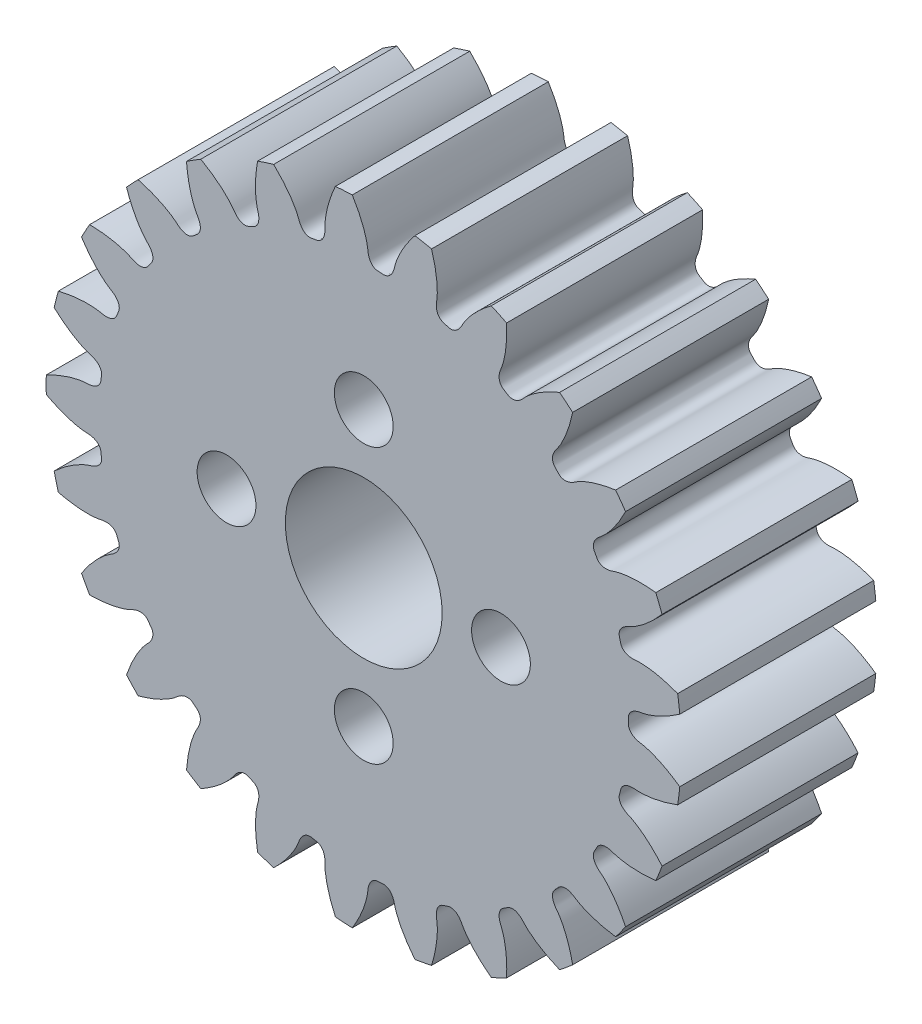
SolidWorks part; units mm, degrees
material "Д16 ГОСТ 4784-97"
ref_plane "FRONT" through (0, 0, 0) normal (0, 0, 1) x (1, 0, 0)
ref_plane "TOP" through (0, 0, 0) normal (0, 1, 0) x (1, 0, 0)
ref_plane "RIGHT" through (0, 0, 0) normal (1, 0, 0) x (0, 0, -1)
ref_axis "Ось1" through (0, 0, 50) along (0, 0, -1)
sketch "SketchRevolveSpurPinion" plane through (0, 0, 0) normal (1, 0, 0) x (0, 0, -1)
  line L0 (0, 0) -> (1, 0) construction
  line L1 (-5, 0) -> (-5, 16.2)
  line L2 (-5, 16.2) -> (5, 16.2)
  line L3 (5, 16.2) -> (5, 0)
  line L4 (5, 0) -> (-5, 0)
revolve "SpurPinion" add sketch "SketchRevolveSpurPinion" angle 360 about L0
sketch "SketchToothSpurPinion" plane through (0, 0, 0) normal (0, 0, 1) x (1, 0, 0)
  arc A0 (16.1769, 1.6413) -> (16.1769, -1.6413) centre (0, 0) cw
  spline S0 degree 3 poles (16.1769, -1.6413) (16.0571, -1.5552) (15.8785, -1.4341) (15.6403, -1.2876) (15.4737, -1.1915) (15.3146, -1.1059) (15.1636, -1.03) (15.021, -0.9635) (14.8873, -0.9057) (14.7627, -0.8561) (14.6478, -0.814) (14.5428, -0.779) (14.4479, -0.7504) (14.3636, -0.7275) (14.2899, -0.7099) (14.1891, -0.6884) (14.1006, -0.6766) (14.0235, -0.6588) (13.9906, -0.6504) (13.9585, -0.6412) (13.9271, -0.6311) (13.8962, -0.6202) (13.8659, -0.6084) (13.8361, -0.5955) (13.8068, -0.5814) (13.7778, -0.5661) (13.7492, -0.5492) (13.7209, -0.5305) (13.6928, -0.5098) (13.6651, -0.4868) (13.6378, -0.4609) (13.6112, -0.4318) (13.5856, -0.3991) (13.5616, -0.3622) (13.5401, -0.321) (13.522, -0.2755) (13.5085, -0.2261) (13.5011, -0.1771) (13.4979, -0.1014) (13.5016, 0) (13.4979, 0.1014) (13.5011, 0.1771) (13.5085, 0.2261) (13.522, 0.2755) (13.5401, 0.321) (13.5616, 0.3622) (13.5856, 0.3991) (13.6112, 0.4318) (13.6378, 0.4609) (13.6651, 0.4868) (13.6928, 0.5098) (13.7209, 0.5305) (13.7492, 0.5492) (13.7778, 0.5661) (13.8068, 0.5814) (13.8361, 0.5955) (13.8659, 0.6084) (13.8962, 0.6202) (13.9271, 0.6311) (13.9585, 0.6412) (13.9906, 0.6504) (14.0235, 0.6588) (14.1006, 0.6766) (14.1891, 0.6884) (14.2899, 0.7099) (14.3636, 0.7275) (14.4479, 0.7504) (14.5428, 0.779) (14.6478, 0.814) (14.7627, 0.8561) (14.8873, 0.9057) (15.021, 0.9635) (15.1636, 1.03) (15.3146, 1.1059) (15.4737, 1.1915) (15.6403, 1.2876) (15.8785, 1.4341) (16.0571, 1.5552) (16.1769, 1.6413) knots 0 0 0 0 0.066592 0.09726 0.126175 0.153338 0.178748 0.202406 0.224312 0.244465 0.262865 0.279513 0.294409 0.307552 0.318943 0.328581 0.35401 0.359185 0.364277 0.369297 0.374256 0.379169 0.384052 0.388923 0.393806 0.398725 0.40371 0.408794 0.414018 0.419423 0.425056 0.430965 0.437198 0.443793 0.450773 0.458134 0.46584 0.473813 0.480451 0.5 0.519549 0.526187 0.53416 0.541866 0.549227 0.556207 0.562802 0.569035 0.574944 0.580577 0.585982 0.591206 0.59629 0.601275 0.606194 0.611077 0.615948 0.620831 0.625744 0.630703 0.635723 0.640815 0.64599 0.671419 0.681057 0.692448 0.705591 0.720487 0.737135 0.755535 0.775688 0.797594 0.821252 0.846662 0.873825 0.90274 0.933408 1 1 1 1
extrude "ToothExtrudeCutSpurPinion" cut sketch "SketchToothSpurPinion" against normal blind 5 and the other way blind 5
pattern_circular "PatternSpurPinion" count 25 every 14.4 about axis through (0, 0, 50) along (0, 0, -1) of "ToothExtrudeCutSpurPinion"
sketch "AuxiliarySketchSpurPinion" plane through (0, 0, 0) normal (0, 0, 1) x (1, 0, 0)
  circle A0 centre (0, 0) radius 15 construction
  circle A1 centre (0, 0) radius 14.0954 construction
  circle A2 centre (0, 0) radius 14.1685 construction
  circle A3 centre (0, 0) radius 16.2 construction
  circle A4 centre (0, 0) radius 13.5 construction
  dimension "PitchDiameter" = 30
  dimension "BaseDiameter" = 28.1908
  dimension "FormDiameter" = 28.3369
  dimension "MajorDiameter" = 32.4
  dimension "MinorDiameter" = 27
sketch "Эскиз5" plane through (0, 0, 5) normal (0, 0, 1) x (1, 0, 0)
  circle A0 centre (0, 0) radius 7 construction
  circle A1 centre (0, 0) radius 8.5 construction
  circle A2 centre (0, 7) radius 1.5
  circle A3 centre (7, 0) radius 1.5
  circle A4 centre (-7, 0) radius 1.5
  circle A5 centre (0, -7) radius 1.5
  circle A6 centre (0, 0) radius 4
  dimension "D1" = 14
  dimension "D2" = 17
  dimension "D3" = 8
extrude "Вырез-Вытянуть2" cut sketch "Эскиз5" against normal through all
